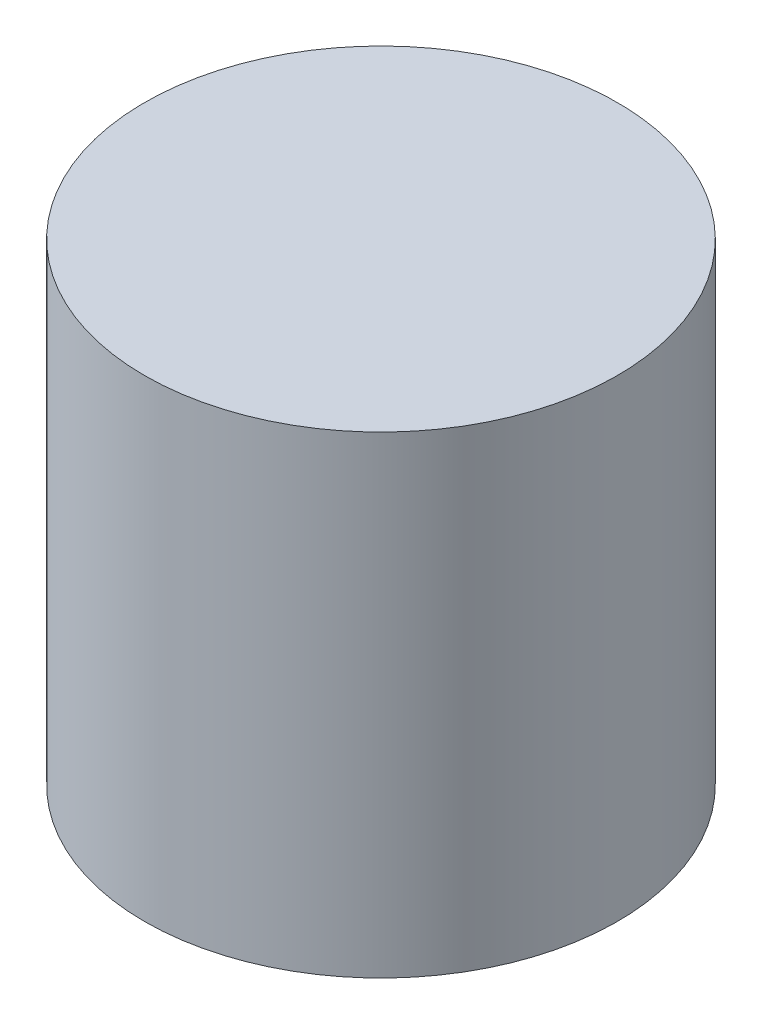
SolidWorks part; units mm, degrees
ref_plane "Front" through (0, 0, 0) normal (0, 0, 1) x (1, 0, 0)
ref_plane "Top" through (0, 0, 0) normal (0, 1, 0) x (1, 0, 0)
ref_plane "Right" through (0, 0, 0) normal (1, 0, 0) x (0, 0, -1)
sketch "Sketch1" plane through (0, 0, 0) normal (0, 1, 0) x (1, 0, 0)
  circle A0 centre (0, 0) radius 50
  dimension "D1" = 100
extrude "Boss-Extrude1" add sketch "Sketch1" along normal blind 100
sketch "Sketch15" plane through (0, 0, 0) normal (0, 0, 1) x (1, 0, 0)
  line L0 (0, 0) -> (0, 100) construction
  line L1 (50, 100) -> (-50, 100) construction
